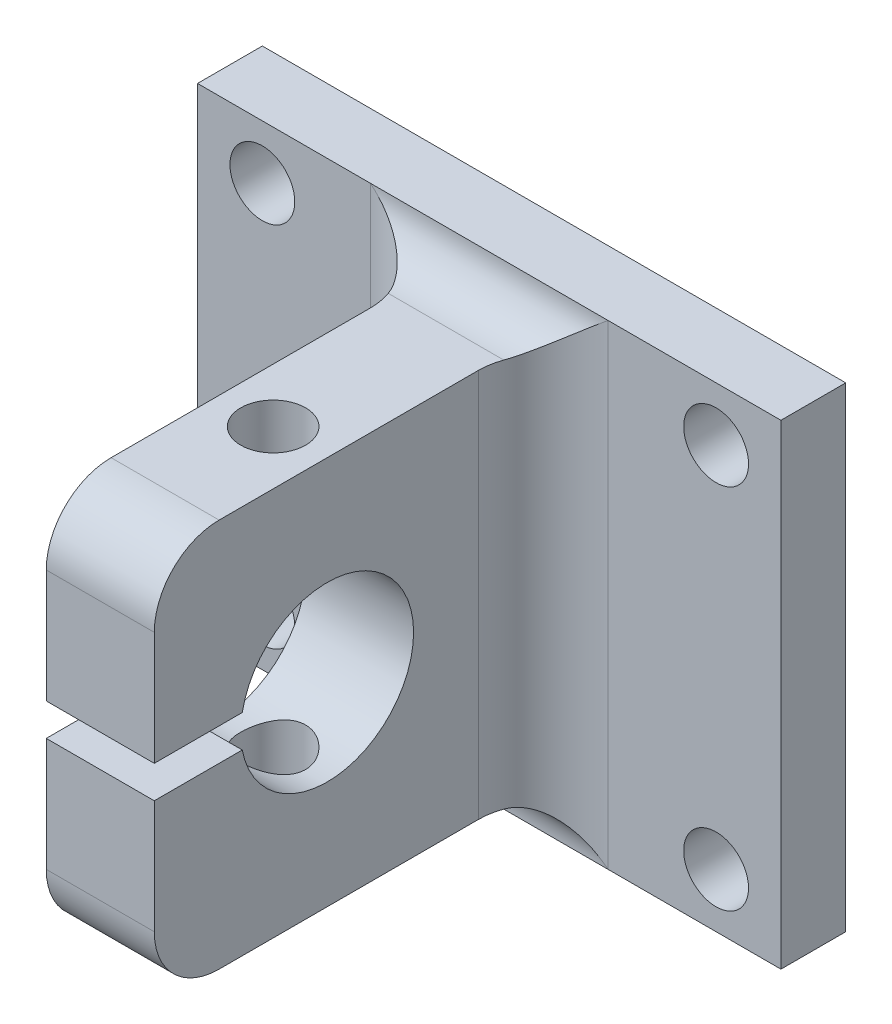
SolidWorks part; units mm, degrees
ref_plane "Front Plane" through (0, 0, 0) normal (0, 0, 1) x (1, 0, 0)
ref_plane "Top Plane" through (0, 0, 0) normal (0, 1, 0) x (1, 0, 0)
ref_plane "Right Plane" through (0, 0, 0) normal (1, 0, 0) x (0, 0, -1)
sketch "Sketch1" plane through (0, 0, 0) normal (0, 0, 1) x (1, 0, 0)
  line L1 (-13.5, -11) -> (13.5, -11)
  line L2 (-13.5, -11) -> (-13.5, 11)
  line L3 (-13.5, 11) -> (13.5, 11)
  line L4 (13.5, -11) -> (13.5, 11)
  line L5 (-13.5, -11) -> (13.5, 11) construction
  line L6 (-13.5, 11) -> (13.5, -11) construction
  line L7 (-10.5, -8.5) -> (-10.5, 8.5) construction
  line L8 (-10.5, 8.5) -> (10.5, 8.5) construction
  circle A5 centre (-10.5, -8.5) radius 1.5
  circle A6 centre (-10.5, 8.5) radius 1.5
  circle A7 centre (10.5, 8.5) radius 1.5
  circle A8 centre (10.5, -8.5) radius 1.5
  point P0 (0, 0)
  point P11 (-13.5, 0)
  point P12 (0, 11)
  point P13 (-10.5, 0)
  point P21 (0, 8.5)
  dimension "D5" = 3
  dimension "D1" = 27
  dimension "D2" = 22
  dimension "D6" = 17
  dimension "D7" = 21
extrude "Boss-Extrude1" add sketch "Sketch1" along normal blind 3
sketch "Sketch2" plane through (0, 0, 3) normal (0, 0, 1) x (1, 0, 0)
  line L1 (-2.5, 9) -> (2.5, 9)
  line L2 (-2.5, 9) -> (-2.5, -9)
  line L3 (-2.5, -9) -> (2.5, -9)
  line L4 (2.5, 9) -> (2.5, -9)
  line L5 (-13.5, -11) -> (13.5, -11) construction
  line L6 (2.5, 3.6093) -> (-2.5, 3.6093) construction
  line L7 (-13.5, 11) -> (-13.5, -11) construction
  point P4 (-13.5, 0)
  point P10 (0, -11)
  point P11 (0, 3.6093)
  point P16 (-2.5, 0)
  dimension "D1" = 5
  dimension "D2" = 18
extrude "Boss-Extrude2" add sketch "Sketch2" along normal blind 18
sketch "Sketch3" plane through (2.5, 0, 0) normal (1, 0, 0) x (0, 0, -1)
  line L0 (-21, -9) -> (-21, 9) construction
  line L1 (-3, -9) -> (-3, 9) construction
  circle A0 centre (-13, 0) radius 4
  point P5 (-21, 0)
  dimension "D1" = 8
  dimension "D2" = 10
extrude "Cut-Extrude1" cut sketch "Sketch3" against normal through all both and the other way through all
sketch "Sketch4" plane through (2.5, 0, 0) normal (1, 0, 0) x (0, 0, -1)
  line L1 (-22.3796, -0.75) -> (-14.282, -0.75)
  line L2 (-22.3796, -0.75) -> (-22.3796, 0.75)
  line L3 (-22.3796, 0.75) -> (-14.282, 0.75)
  line L4 (-14.282, -0.75) -> (-14.282, 0.75)
  line L5 (-21, -9) -> (-21, 9) construction
  point P6 (-21, 0)
  point P7 (-22.3796, 0)
  dimension "D1" = 1.5
extrude "Cut-Extrude2" cut sketch "Sketch4" against normal through all both and the other way through all
sketch "Sketch5" plane through (0, 11, 0) normal (0, 1, 0) x (1, 0, 0)
  line L0 (2.5, -21) -> (-2.5, -21) construction
  line L2 (2.5, -3) -> (-2.5, -3) construction
  circle A0 centre (0, -13) radius 1.5
  point P5 (0, -21)
  dimension "D1" = 3
  dimension "D2" = 10
fillet "Fillet1" radius 3 2 edges at (-2.5, 0, 3) (2.5, 0, 3)
extrude "Cut-Extrude3" cut sketch "Sketch5" against normal through all both and the other way through all
fillet "Fillet2" radius 2 2 edges at (0, 9, 3) (0, -9, 3)
fillet "Fillet3" radius 3 2 edges at (0, -9, 21) (0, 9, 21)
